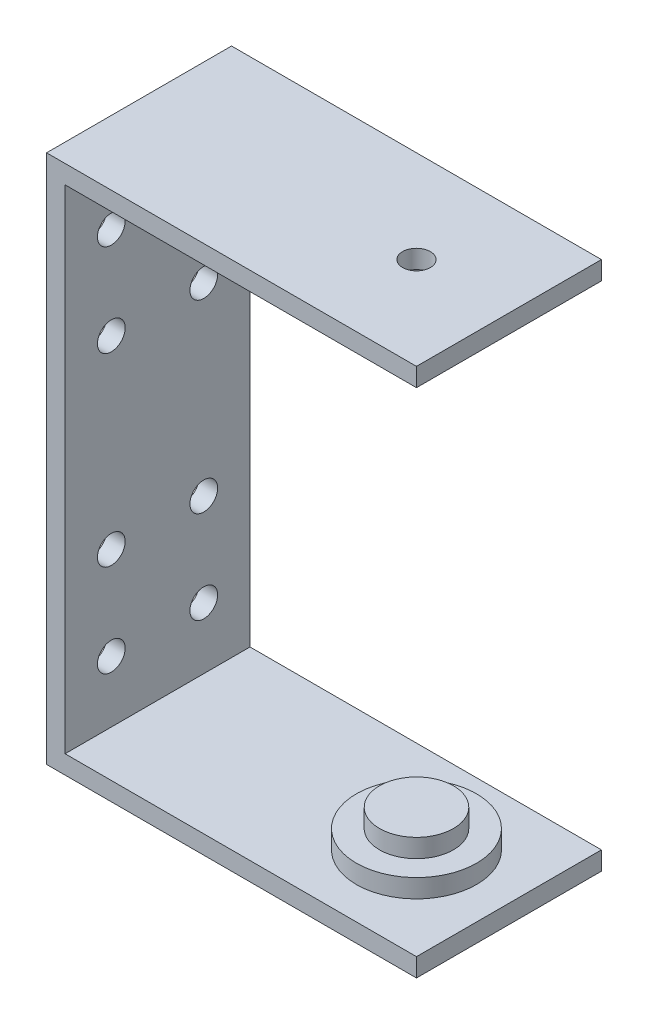
SolidWorks part; units mm, degrees
ref_plane "Front Plane" through (0, 0, 0) normal (0, 0, 1) x (1, 0, 0)
ref_plane "Top Plane" through (0, 0, 0) normal (0, 1, 0) x (1, 0, 0)
ref_plane "Right Plane" through (0, 0, 0) normal (1, 0, 0) x (0, 0, -1)
sketch "Sketch1" plane through (0, 0, 0) normal (0, 1, 0) x (1, 0, 0)
  line L1 (-30, -10) -> (10, -10)
  line L2 (-30, -10) -> (-30, 10)
  line L3 (-30, 10) -> (10, 10)
  line L4 (10, -10) -> (10, 10)
  circle A0 centre (0, 0) radius 2.8
  circle A1 centre (0, 0) radius 4
  circle A2 centre (0, 0) radius 6.5
  circle A4 centre (0, 0) radius 1.5
  point P10 (10, 0)
  dimension "D1" = 8
  dimension "D2" = 13
  dimension "D3" = 5.6
  dimension "D4" = 3
  dimension "D5" = 20
  dimension "D6" = 10
  dimension "D7" = 30
extrude "Boss-Extrude1" add sketch "Sketch1" along normal blind 2 contours A2 A1 | A4 | A0 A4 | A1 A0 region at (-2.7208, 0, 0) region at (-3.8869, 0, 0) region at (-6.3162, 0, 0) region at (0, 0, 0)
extrude "Boss-Extrude2" add sketch "Sketch1<3>" along normal blind 2 from surface contours A1 A0 | A0 A4 | A4 region at (-2.7208, 0, 0) region at (-3.8869, 0, 0) region at (0, 0, 0) starting at face at (0, 2, 6.5)
sketch "Sketch1<3>" plane through (0, 0, 0) normal (0, 1, 0) x (1, 0, 0) same geometry as "Sketch1"
extrude "Boss-Extrude3" add sketch "Sketch1<4>" against normal blind 2 contours L3 L4 L1 L2
sketch "Sketch1<4>" plane through (0, 0, 0) normal (0, 1, 0) x (1, 0, 0) same geometry as "Sketch1"
sketch "Sketch2" plane through (0, 0, 0) normal (0, 1, 0) x (1, 0, 0)
  line L0 (-30, -10) -> (10, -10) construction
  line L1 (-30, 10) -> (-28, 10)
  line L2 (-30, 10) -> (-30, -10)
  line L3 (-30, -10) -> (-28, -10)
  line L4 (-28, 10) -> (-28, -10)
  dimension "D1" = 2
extrude "Boss-Extrude4" add sketch "Sketch2" along normal blind 53.28
extrude "Boss-Extrude5" add sketch "Sketch1<5>" along normal blind 2 from surface contours L1 L4 L3 L2 A2 | A2 A1 | A1 A0 | A0 A4 region at (-11.9892, 0, 0) region at (-2.7208, 0, 0) region at (-3.8869, 0, 0) region at (-6.3162, 0, 0) starting at face at (-29, 53.28, 0)
sketch "Sketch1<5>" plane through (0, 0, 0) normal (0, 1, 0) x (1, 0, 0) same geometry as "Sketch1"
extrude "Boss-Extrude6" add sketch "Sketch1<6>" against normal blind 2 from surface contours A1 A0 region at (-3.8869, 0, 0) starting at face at (-9, 53.28, 0)
sketch "Sketch1<6>" plane through (0, 0, 0) normal (0, 1, 0) x (1, 0, 0) same geometry as "Sketch1"
hole_wizard "Ø3.0mm Dowel Hole1" positions "Sketch3" profile "Sketch4" hole size "Ø3.0" standard "DIN"
sketch "Sketch3" plane through (-30, 0, 0) normal (-1, 0, 0) x (0, 0, 1)
  line L1 (-5, 46.64) -> (5, 46.64) construction
  line L2 (-5, 46.64) -> (-5, 36.64) construction
  line L3 (-5, 36.64) -> (5, 36.64) construction
  line L4 (5, 46.64) -> (5, 36.64) construction
  line L6 (-5, 16.64) -> (5, 16.64) construction
  line L7 (-5, 16.64) -> (-5, 6.64) construction
  line L8 (-5, 6.64) -> (5, 6.64) construction
  line L9 (5, 16.64) -> (5, 6.64) construction
  line L11 (-10, 55.28) -> (10, 55.28) construction
  line L12 (0, 36.64) -> (0, 16.64) construction
  line L14 (10, -2) -> (10, 55.28) construction
  point P0 (-5, 46.64)
  point P2 (5, 46.64)
  point P86 (-5, 36.64)
  point P88 (5, 36.64)
  point P90 (-5, 16.64)
  point P92 (5, 16.64)
  point P94 (-5, 6.64)
  point P96 (5, 6.64)
  point P195 (0, 55.28)
  point P196 (0, 46.64)
  point P197 (0, 16.64)
  point P211 (10, 26.64)
  point P212 (0, 26.64)
  dimension "D1" = 10
  dimension "D2" = 20
sketch "Sketch4" plane through (-30, 46.64, -5) normal (0, 1, 0) x (0, 0, 1)
  line L0 (0, 0) -> (0, 7.9013)
  line L1 (0, 7.9013) -> (1.5, 7)
  line L2 (1.5, 7) -> (1.5, 0)
  line L5 (1.5, 0) -> (0, 0)
  line L10 (0, 7.9013) -> (-1.5, 7) construction
  line L11 (0, -6.35) -> (0, 107.95) construction
  dimension "Hole Dia." = 3
  dimension "Hole Depth" = 7
  dimension "Drill Angle" = 118
